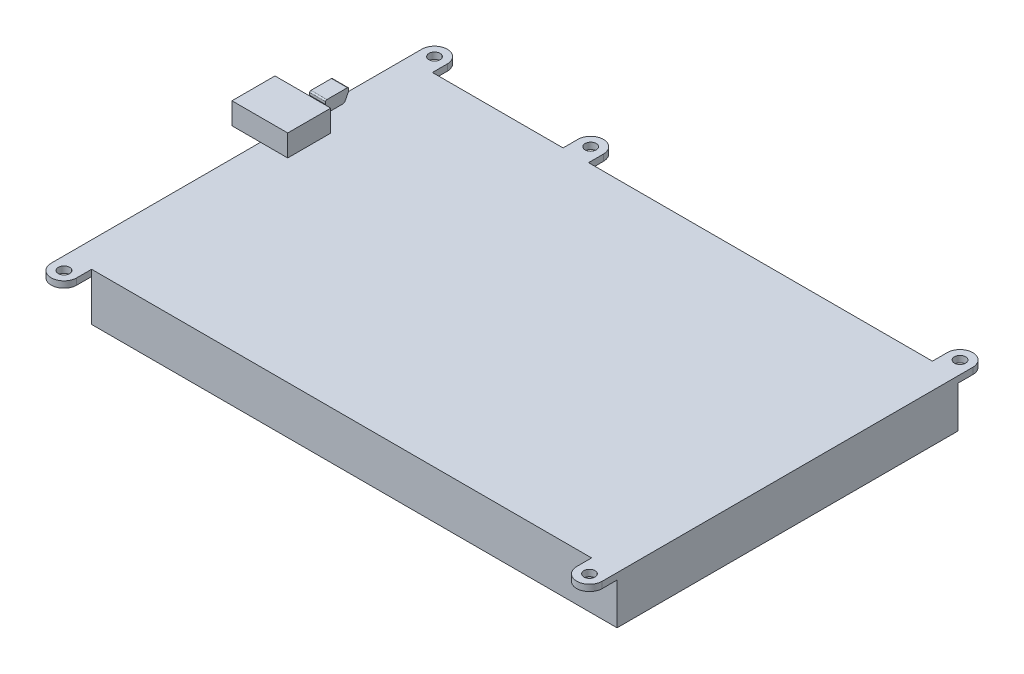
SolidWorks part; units mm, degrees
ref_plane "Front Plane" through (0, 0, 0) normal (0, 0, 1) x (1, 0, 0)
ref_plane "Top Plane" through (0, 0, 0) normal (0, 1, 0) x (1, 0, 0)
ref_plane "Right Plane" through (0, 0, 0) normal (1, 0, 0) x (0, 0, -1)
sketch "Sketch1" plane through (0, 0, 0) normal (0, 1, 0) x (1, 0, 0)
  line L1 (82.45, 53.475) -> (-82.45, 53.475)
  line L2 (82.45, 53.475) -> (82.45, -53.475)
  line L3 (82.45, -53.475) -> (-82.45, -53.475)
  line L4 (-82.45, 53.475) -> (-82.45, -53.475)
  line L5 (82.45, 53.475) -> (-82.45, -53.475) construction
  line L6 (82.45, -53.475) -> (-82.45, 53.475) construction
  point P0 (0, 0)
  dimension "D1" = 106.95
  dimension "D2" = 164.9
extrude "Boss-Extrude1" add sketch "Sketch1" along normal mid plane 15 from surface contours L1 L4 L3 L2 starting at plane "Top Plane"
sketch "Sketch3" plane through (0, 7.5, 0) normal (0, 1, 0) x (1, 0, 0)
  line L0 (0, -62.135) -> (0, 62.135) construction
  line L2 (0, -13.2093) -> (0, 13.2093) construction
  line L6 (-90.45, -62.135) -> (-82.45, -62.135)
  line L8 (-90.45, 62.135) -> (-82.45, 62.135)
  line L9 (-90.45, 62.135) -> (-90.45, -62.135)
  line L11 (-82.45, 62.135) -> (-82.45, -62.135)
  dimension "D1" = 62.135
  dimension "D2" = 124.27
extrude "Boss-Extrude2" add sketch "Sketch3" against normal blind 2
fillet "Fillet1" 2 edges at (-90.45, 6.5, -62.135) (-82.45, 6.5, -62.135) type full round first side face at (-90.45, 6.5, 0) second side face at (-82.45, 6.5, -57.805) middle face at (-86.45, 6.5, -62.135)
fillet "Fillet2" 2 edges at (-90.45, 6.5, 62.135) (-82.45, 6.5, 62.135) type full round first side face at (-90.45, 6.5, 2) second side face at (-82.45, 6.5, 57.805) middle face at (-86.45, 6.5, 62.135)
hole_wizard "Ø3.0mm Dowel Hole2" positions "Sketch5" profile "Sketch6" hole size "Ø3.0" standard "ANSI Metric" end condition up to next
sketch "Sketch5" plane through (0, 7.5, 0) normal (0, 1, 0) x (1, 0, 0)
  point P8 (-86.45, 58.135)
sketch "Sketch6" plane through (-86.45, 7.5, -58.135) normal (1, 0, 0) x (0, 0, 1)
  line L0 (0, 0) -> (0, 15)
  line L1 (0, 15) -> (1.75, 15)
  line L2 (1.75, 15) -> (1.75, 0)
  line L5 (1.75, 0) -> (0, 0)
  line L11 (0, -6.35) -> (0, 107.95) construction
  dimension "Thru Hole Dia." = 3.5
  dimension "Thru Hole Depth" = 15
mirror "Mirror5" about plane through (0, 0, 0) normal (0, 0, 1) of "Ø3.0mm Dowel Hole2"
sketch "Sketch11" plane through (0, 7.5, 0) normal (0, 1, 0) x (1, 0, 0)
  line L0 (-86.45, 62.135) -> (-86.45, 53.475) construction
  line L1 (-41.45, 62.135) -> (-33.45, 62.135)
  line L2 (-41.45, 62.135) -> (-41.45, 53.475)
  line L3 (-33.45, 62.135) -> (-33.45, 53.475)
  line L4 (-41.45, 53.475) -> (-33.45, 53.475)
  arc A0 (-82.45, 58.135) -> (-90.45, 58.135) centre (-86.45, 58.135) ccw construction
  point P2 (-37.45, 62.135)
  dimension "D1" = 8
  dimension "D2" = 8.66
  dimension "D3" = 49
mirror "Mirror6" about plane through (0, 0, 0) normal (0, 0, 1) of "Ø3.0mm Dowel Hole2"
extrude "Boss-Extrude4" add sketch "Sketch11" against normal blind 2
fillet "Fillet3" 2 edges at (-41.45, 6.5, -62.135) (-33.45, 6.5, -62.135) type full round first side face at (-41.45, 6.5, -57.805) second side face at (-33.45, 6.5, -57.805) middle face at (-37.45, 6.5, -62.135)
hole_wizard "Ø3.0mm Dowel Hole4" positions "Sketch14" profile "Sketch15" hole size "Ø3.0" standard "ANSI Metric" end condition up to next
sketch "Sketch14" plane through (0, 5.5, 0) normal (0, -1, 0) x (-1, 0, 0)
  point P0 (37.45, 58.135)
sketch "Sketch15" plane through (-37.45, 5.5, -58.135) normal (1, 0, 0) x (0, 0, -1)
  line L0 (0, 0) -> (0, 2)
  line L1 (0, 2) -> (1.75, 2)
  line L2 (1.75, 2) -> (1.75, 0)
  line L5 (1.75, 0) -> (0, 0)
  line L11 (0, -6.35) -> (0, 107.95) construction
  dimension "Thru Hole Dia." = 3.5
  dimension "Thru Hole Depth" = 2
sketch "Sketch16" plane through (0, 7.5, 0) normal (0, -1, 0) x (1, 0, 0)
  line L0 (82.45, -53.475) -> (82.45, -62.135)
  line L1 (82.45, -62.135) -> (74.45, -62.135)
  line L2 (74.45, -62.135) -> (74.45, -53.475)
  line L3 (-82.45, -53.475) -> (82.45, -53.475) construction
  line L4 (74.45, -53.475) -> (82.45, -53.475)
  dimension "D1" = 8.66
  dimension "D2" = 8
extrude "Boss-Extrude5" add sketch "Sketch16" along normal blind 2
fillet "Fillet6" 2 edges at (82.45, 6.5, -62.135) (74.45, 6.5, -62.135) type full round first side face at (82.45, 1.8333, -20.7117) second side face at (74.45, 6.5, -57.805) middle face at (78.45, 6.5, -62.135)
mirror "Mirror10" about plane through (0, 0, 0) normal (0, 0, 1) of "Boss-Extrude5"
fillet "Fillet7" 2 edges at (74.45, 6.5, 62.135) (82.45, 6.5, 62.135) type full round first side face at (74.45, 6.5, 57.805) second side face at (82.45, 2.75, 1) middle face at (78.45, 6.5, 62.135)
hole_wizard "Ø3.0mm Dowel Hole7" positions "Sketch21" profile "Sketch22" hole size "Ø3.0" standard "ANSI Metric" end condition up to next
sketch "Sketch21" plane through (0, 5.5, 0) normal (0, -1, 0) x (-1, 0, 0)
  point P0 (-78.45, 58.135)
sketch "Sketch22" plane through (78.45, 5.5, -58.135) normal (1, 0, 0) x (0, 0, -1)
  line L0 (0, 0) -> (0, 2)
  line L1 (0, 2) -> (1.75, 2)
  line L2 (1.75, 2) -> (1.75, 0)
  line L5 (1.75, 0) -> (0, 0)
  line L11 (0, -6.35) -> (0, 107.95) construction
  dimension "Thru Hole Dia." = 3.5
  dimension "Thru Hole Depth" = 2
hole_wizard "Ø3.0mm Dowel Hole8" positions "Sketch23" profile "Sketch24" hole size "Ø3.0" standard "ANSI Metric" end condition up to next
sketch "Sketch23" plane through (0, 7.5, 0) normal (0, 1, 0) x (1, 0, 0)
  point P0 (78.45, -58.135)
sketch "Sketch24" plane through (78.45, 7.5, 58.135) normal (1, 0, 0) x (0, 0, 1)
  line L0 (0, 0) -> (0, 2)
  line L1 (0, 2) -> (1.75, 2)
  line L2 (1.75, 2) -> (1.75, 0)
  line L5 (1.75, 0) -> (0, 0)
  line L11 (0, -6.35) -> (0, 107.95) construction
  dimension "Thru Hole Dia." = 3.5
  dimension "Thru Hole Depth" = 2
sketch "Sketch26" plane through (-90.45, 0, 0) normal (-1, 0, 0) x (0, 0, 1)
  line L0 (-30.8636, 7.5) -> (-27.2764, 7.5)
  line L4 (-32.67, 10.8) -> (-32.67, 10.0994)
  line L6 (-25.47, 10.8) -> (-25.47, 10.0994)
  line L7 (-32.27, 11.2) -> (-25.87, 11.2)
  line L13 (-26.5696, 7.9254) -> (-25.5166, 9.9121)
  line L14 (-31.5704, 7.9254) -> (-32.6234, 9.9121)
  line L15 (-58.135, 7.5) -> (0, 7.5) construction
  line L17 (-58.135, 11.2) -> (0, 11.2) construction
  arc A0 (-25.47, 10.8) -> (-25.87, 11.2) centre (-25.87, 10.8) ccw
  arc A1 (-32.6234, 9.9121) -> (-32.67, 10.0994) centre (-32.27, 10.0994) cw
  arc A2 (-32.67, 10.8) -> (-32.27, 11.2) centre (-32.27, 10.8) cw
  arc A3 (-25.5166, 9.9121) -> (-25.47, 10.0994) centre (-25.87, 10.0994) ccw
  arc A4 (-27.2764, 7.5) -> (-26.5696, 7.9254) centre (-27.2764, 8.3) ccw
  arc A5 (-30.8636, 7.5) -> (-31.5704, 7.9254) centre (-30.8636, 8.3) cw
  dimension "D1" = 0.4
  dimension "D4" = 0.8
  dimension "D3" = 3.7
extrude "Boss-Extrude7" add sketch "Sketch26" against normal mid plane 5 from surface starting at face at (-90.45, 6.5, 0)
sketch "Sketch28" plane through (-90.45, 0, 0) normal (-1, 0, 0) x (0, 0, 1)
  line L6 (-32.27, 11) -> (-25.87, 11)
  line L7 (-25.67, 10.8) -> (-25.67, 10.0994)
  line L8 (-26.7463, 8.019) -> (-25.6933, 10.0058)
  line L9 (-30.8636, 7.7) -> (-27.2764, 7.7)
  line L10 (-32.4467, 10.0058) -> (-31.3937, 8.019)
  line L21 (-32.4578, 10.8) -> (-32.4578, 10.0994)
  arc A7 (-32.4578, 10.8) -> (-32.27, 11) centre (-32.27, 10.8118) cw
  arc A8 (-32.4467, 10.0058) -> (-32.4578, 10.0994) centre (-32.0578, 10.0994) cw
  arc A9 (-31.3937, 8.019) -> (-30.8636, 7.7) centre (-30.7483, 8.4916) ccw
  arc A11 (-27.2764, 7.7) -> (-26.7463, 8.019) centre (-27.3917, 8.4916) ccw
  arc A12 (-25.67, 10.0994) -> (-25.6933, 10.0058) centre (-26.067, 10.1484) cw
  arc A13 (-25.87, 11) -> (-25.67, 10.8) centre (-25.87, 10.8) cw
  dimension "D7" = 0.8
  dimension "D6" = 0.4
  dimension "D8" = 0.4
  dimension "D9" = 0.8
extrude "Cut-Extrude4" cut sketch "Sketch28" against normal blind 4.95 from surface starting at face at (-92.95, 9.5698, -29.07)
sketch "Sketch29" plane through (-88, 0, 0) normal (-1, 0, 0) x (0, 0, 1)
  line L0 (-31.07, 10.8) -> (-27.07, 10.8)
  line L1 (-30.8636, 7.7) -> (-27.2764, 7.7) construction
  line L2 (-25.87, 11) -> (-32.27, 11) construction
  line L3 (-31.07, 10.6) -> (-27.07, 10.6)
  line L4 (-31.07, 10.6) -> (-31.07, 10.8)
  line L5 (-27.07, 10.6) -> (-27.07, 10.8)
  point P2 (-29.07, 10.8)
  point P5 (-29.07, 7.7)
  dimension "D1" = 4
  dimension "D2" = 0
  dimension "D3" = 0.2
  dimension "D4" = 0.2
extrude "Boss-Extrude8" add sketch "Sketch29" along normal mid plane 4.95 from surface starting at face at (-90.45, 6.8333, -9.69)
sketch "Sketch30" plane through (-90.45, 0, 0) normal (-1, 0, 0) x (0, 0, 1)
  line L7 (-20.82, 14.5168) -> (-20.82, 7.7168)
  line L10 (-7.32, 14.5168) -> (-7.32, 7.7168)
  line L11 (-20.82, 7.7168) -> (-7.32, 7.7168)
  line L15 (-20.82, 14.5168) -> (-7.32, 14.5168)
  dimension "D1" = 6.8
extrude "Boss-Extrude9" add sketch "Sketch30" against normal mid plane 17.5 from surface separate body starting at face at (-90.45, 6.8333, -9.69)
sketch "Sketch31" plane through (-99.2, 0, 0) normal (-1, 0, 0) x (0, 0, 1)
  line L1 (-7.32, 14.5168) -> (-20.82, 14.5168) construction
  line L7 (-20.62, 9.4168) -> (-7.52, 9.4168)
  line L9 (-20.62, 14.3168) -> (-7.52, 14.3168)
  line L10 (-20.82, 9.4168) -> (-7.32, 9.4168) construction
  line L12 (-20.82, 7.7168) -> (-7.32, 7.7168) construction
  line L13 (-20.62, 14.3168) -> (-20.62, 9.4168)
  line L14 (-7.52, 14.3168) -> (-7.52, 9.4168)
  line L17 (-20.82, 14.3168) -> (-7.32, 14.3168) construction
  dimension "D2" = 1.7
  dimension "D1" = 13.1
  dimension "D3" = 0.2
extrude "Cut-Extrude5" cut sketch "Sketch31" against normal blind 17
sketch "Sketch32" plane through (-82.2, 0, 0) normal (-1, 0, 0) x (0, 0, 1)
  line L0 (-7.52, 14.3168) -> (-20.62, 14.3168) construction
  line L1 (-19.3013, 13.5168) -> (-8.6013, 13.5168)
  line L2 (-20.62, 14.3168) -> (-20.62, 9.4168) construction
  line L3 (-19.3013, 13.5168) -> (-19.3013, 11.7168)
  line L4 (-8.6013, 13.5168) -> (-8.6013, 11.7168)
  line L5 (-19.3013, 11.7168) -> (-8.6013, 11.7168)
  line L6 (-20.62, 11.7168) -> (-7.2826, 11.7168) construction
  line L7 (-20.62, 13.5168) -> (-7.2826, 13.5168) construction
  dimension "D1" = 0.8
  dimension "D2" = 10.7
  dimension "D3" = 1.3187
  dimension "D4" = 1.8
extrude "Boss-Extrude10" add sketch "Sketch32" along normal blind 17
